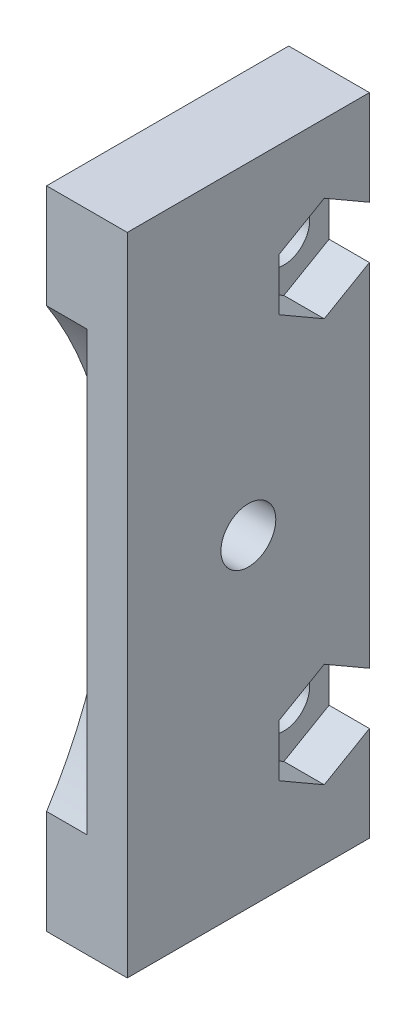
SolidWorks part; units mm, degrees
ref_plane "Front" through (0, 0, 0) normal (0, 0, 1) x (1, 0, 0)
ref_plane "Top" through (0, 0, 0) normal (0, 1, 0) x (1, 0, 0)
ref_plane "Right" through (0, 0, 0) normal (1, 0, 0) x (0, 0, -1)
sketch "Sketch1" plane through (0, 0, 0) normal (1, 0, 0) x (0, 0, -1)
  line L0 (7.5, 40) -> (7.5, 0)
  line L1 (0, 0) -> (15, 0)
  line L2 (0, 0) -> (0, 40)
  line L3 (0, 40) -> (15, 40)
  line L4 (15, 0) -> (15, 40)
  line L5 (12.2, 29.2668) -> (15, 30.8834)
  line L6 (15, 30.8834) -> (15, 34.1166)
  line L7 (15, 34.1166) -> (12.2, 35.7332)
  line L8 (12.2, 35.7332) -> (9.4, 34.1166)
  line L9 (9.4, 34.1166) -> (9.4, 30.8834)
  line L10 (9.4, 30.8834) -> (12.2, 29.2668)
  line L11 (12.2, 4.2668) -> (15, 5.8834)
  line L12 (15, 5.8834) -> (15, 9.1166)
  line L13 (15, 9.1166) -> (12.2, 10.7332)
  line L14 (12.2, 10.7332) -> (9.4, 9.1166)
  line L15 (9.4, 9.1166) -> (9.4, 5.8834)
  line L16 (9.4, 5.8834) -> (12.2, 4.2668)
  circle A0 centre (12.2, 32.5) radius 2.8 construction
  circle A1 centre (12.2, 7.5) radius 2.8 construction
  circle A2 centre (7.5, 8) radius 1.6
  circle A3 centre (7.5, 20) radius 1.7
  circle A4 centre (12.2, 32.5) radius 1.6
  circle A5 centre (12.2, 7.5) radius 1.6
  dimension "D3" = 2.8
  dimension "D7" = 20
  dimension "D1" = 15
  dimension "D2" = 40
  dimension "D4" = 2.8
  dimension "D5" = 7.5
  dimension "D6" = 7.5
  dimension "D8" = 8
extrude "Boss-Extrude1" add sketch "Sketch1" along normal blind 2.5 contours A3 L0 L3 L2 L1 A2 | A3 L0 A2 L1 L4 L11 L16 L15 L14 L13 L5 L10 L9 L8 L7 L3 | L0 A2 | L0 A2 region at (0, 20.2035, -11.1424) region at (0, 20.1656, -3.6605) region at (0, 8, -8.1791) region at (0, 8, -6.8209)
extrude "Boss-Extrude2" add sketch "Sketch1<3>" against normal blind 2.5 contours A3 L0 A2 L1 L4 L11 L16 L15 L14 L13 L5 L10 L9 L8 L7 L3 | A3 L0 L3 L2 L1 A2 | L15 L16 L11 L4 L13 L14 A5 | L9 L10 L5 L4 L7 L8 A4 | A2 region at (0, 20.2035, -11.1424) region at (0, 20.1656, -3.6605) region at (0, 32.5, -14.9145) region at (0, 7.5, -14.9145)
sketch "Sketch1<3>" plane through (0, 0, 0) normal (1, 0, 0) x (0, 0, -1) same geometry as "Sketch1"
sketch "Sketch2" plane through (-2.5, 0, 0) normal (-1, 0, 0) x (0, 0, 1)
  line L0 (-15, 34.948) -> (-15, 29.8031)
  line L1 (-15, 0) -> (-15, 40) construction
  line L2 (-15, 29.8031) -> (-15, 3.7859)
  circle A0 centre (-12.2, 7.5) radius 1.6
  circle A1 centre (-12.2, 32.5) radius 1.6
  circle A2 centre (-12.2, 32.5) radius 3.6
  circle A3 centre (-12.2, 7.5) radius 3.6
  circle M7 centre (-12.2, 32.5) radius 1.6
  circle M8 centre (-12.2, 7.5) radius 1.6
  dimension "D1" = 2
  dimension "D2" = 2
sketch "Sketch3" plane through (-2.5, 0, 0) normal (-1, 0, 0) x (0, 0, 1)
  line L0 (-7.5, 20) -> (21, 20)
  circle A0 centre (21, 20) radius 25
  line M3 (0, 0) -> (0, 40)
  dimension "D1" = 28.5
extrude "Cut-Extrude1" cut sketch "Sketch3" against normal blind 2.5 contours L0 A0 M3 | A0 L0 M3 region at (-2.5, 25.1458, -1.6115) region at (-2.5, 14.8542, -1.6115)
extrude "Boss-Extrude3" add sketch "Sketch2" along normal blind 1 contours L0 A2 M7 | L2 A3 M8 region at (-2.5, 35.8033, -11.0321) region at (-2.5, 10.8033, -11.0321)
